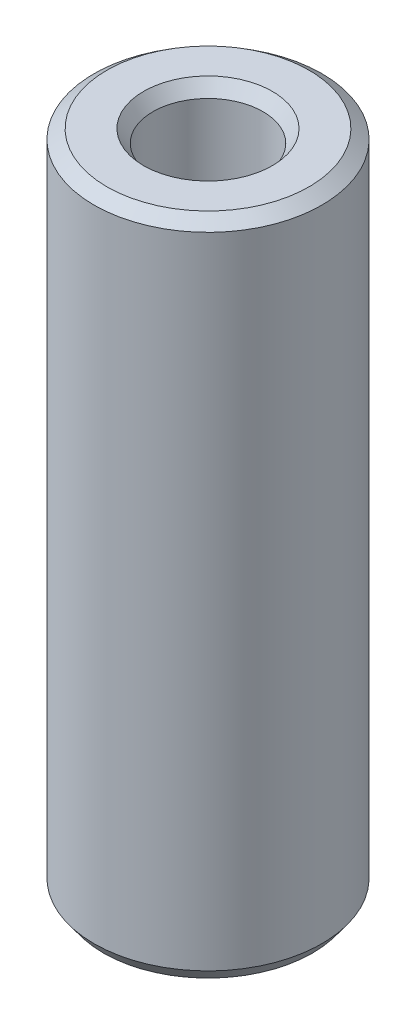
SolidWorks part; units mm, degrees
ref_plane "Front Plane" through (0, 0, 0) normal (0, 0, 1) x (1, 0, 0)
ref_plane "Top Plane" through (0, 0, 0) normal (0, 1, 0) x (1, 0, 0)
ref_plane "Right Plane" through (0, 0, 0) normal (1, 0, 0) x (0, 0, -1)
sketch "Sketch1" plane through (0, 0, 0) normal (0, 1, 0) x (1, 0, 0)
  circle A0 centre (0, 0) radius 42.5
  dimension "SLEEVE_OD" = 85
extrude "Boss-Extrude1" add sketch "Sketch1" along normal blind 246.9385
sketch "Sketch2" plane through (0, 0, 0) normal (0, 1, 0) x (1, 0, 0)
  circle A0 centre (0, 0) radius 20.5213
  dimension "BORE_D" = 41.0425
extrude "Cut-Extrude1" cut sketch "Sketch2" along normal through all
chamfer "Chamfer1" distance 3.5048 angle 53.835 4 edges at (0, 246.9385, 20.5213) (0, 0, 20.5213) (0, 0, 42.5) (0, 246.9385, 42.5) first distance on face at (0, 246.9385, 20.5213) first distance on face at (0, 0, 20.5213) first distance on face at (0, 246.9385, 42.5)
